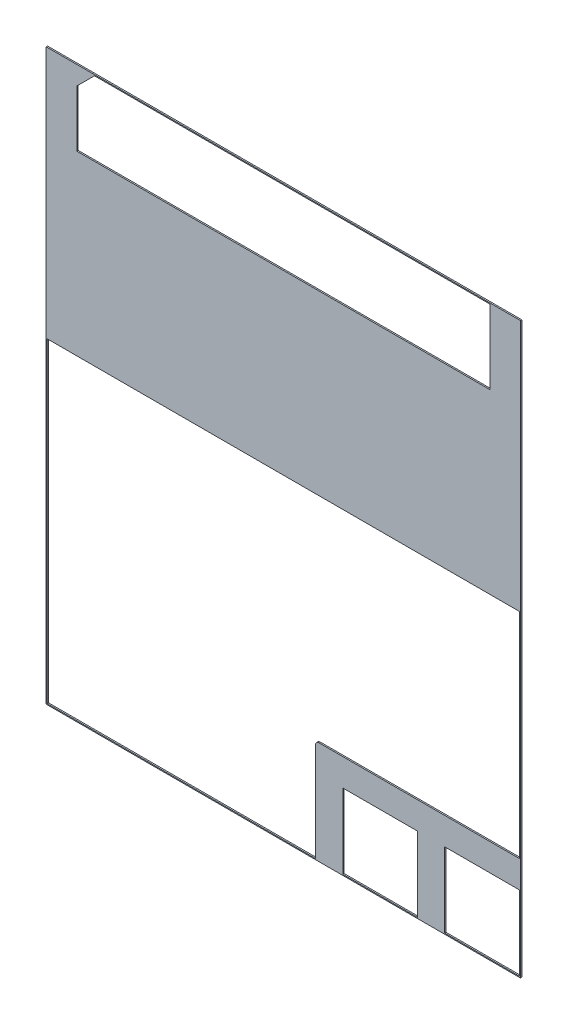
SolidWorks part; units mm, degrees
ref_plane "Ön Düzlem" through (0, 0, 0) normal (0, 0, 1) x (1, 0, 0)
ref_plane "Üst Düzlem" through (0, 0, 0) normal (0, 1, 0) x (1, 0, 0)
ref_plane "Sağ Düzlem" through (0, 0, 0) normal (1, 0, 0) x (0, 0, -1)
ref_plane "Plane1" through (0, 0, 0) normal (0, 0, -1) x (-1, 0, 0)
sketch "Sketch1" plane through (0, 0, 0) normal (0, 0, -1) x (-1, 0, 0)
  line L0 (-6.705, 0.015) -> (-6.705, 1.115)
  line L1 (-6.705, 1.115) -> (-5.605, 1.115)
  line L2 (-5.605, 1.115) -> (-5.605, 0.015)
  line L3 (-5.605, 0.015) -> (-6.705, 0.015)
  line L4 (-5.205, 0.015) -> (-5.205, 1.115)
  line L5 (-5.205, 1.115) -> (-4.105, 1.115)
  line L6 (-4.105, 1.115) -> (-4.105, 0.015)
  line L7 (-4.105, 0.015) -> (-5.205, 0.015)
  line L8 (-6.72, 0) -> (0.26, 0)
  line L9 (0.26, 0) -> (0.26, 8.38)
  line L10 (0.26, 8.38) -> (-6.72, 8.38)
  line L11 (-6.72, 8.38) -> (-6.72, 0)
  line L12 (-3.755, 1.515) -> (-6.705, 1.515)
  line L13 (-6.705, 1.515) -> (-6.705, 4.665)
  line L14 (-6.705, 4.665) -> (0.245, 4.665)
  line L15 (0.245, 4.665) -> (0.245, 0.015)
  line L16 (0.245, 0.015) -> (-3.705, 0.015)
  line L17 (-3.705, 0.015) -> (-3.705, 1.465)
  line L18 (-0.19, 8.105) -> (-0.19, 7.275)
  line L19 (-0.19, 7.275) -> (-6.27, 7.275)
  line L20 (-6.27, 7.275) -> (-6.27, 8.365)
  line L21 (-6.27, 8.365) -> (-0.45, 8.365)
  line L22 (-0.45, 8.365) -> (-0.19, 8.105)
  arc A0 (-3.705, 1.465) -> (-3.755, 1.515) centre (-3.755, 1.465) ccw
extrude "Boss-Extrude1" add sketch "Sketch1" against normal blind 0.02
